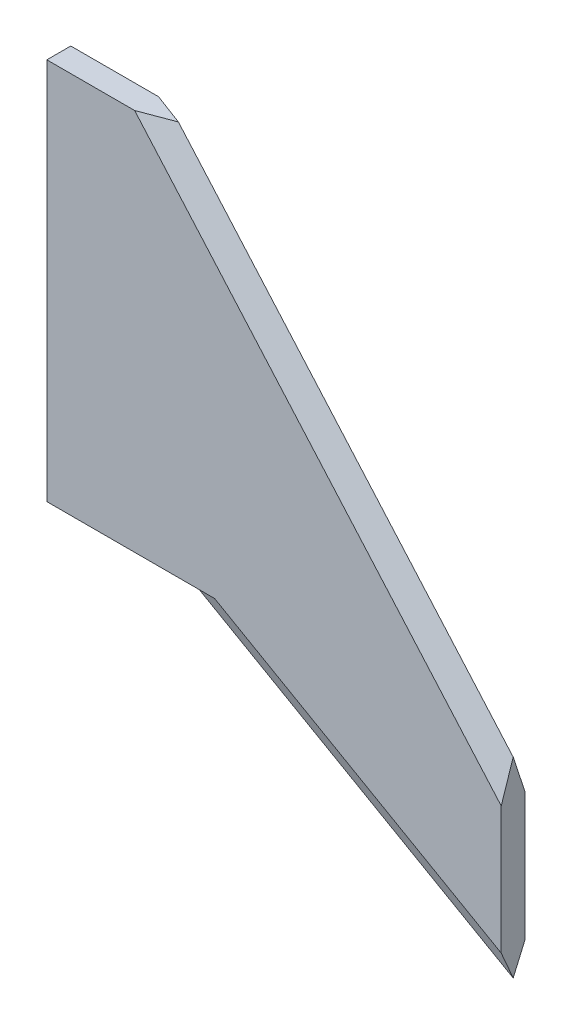
SolidWorks part; units mm, degrees
ref_plane "Front Plane" through (0, 0, 0) normal (0, 0, 1) x (1, 0, 0)
ref_plane "Top Plane" through (0, 0, 0) normal (0, 1, 0) x (1, 0, 0)
ref_plane "Right Plane" through (0, 0, 0) normal (1, 0, 0) x (0, 0, -1)
sketch "Sketch1" plane through (0, 0, 0) normal (0, 0, 1) x (1, 0, 0)
  line L0 (0, 0) -> (0, 80)
  line L1 (0, 80) -> (70, 0)
  line L2 (70, 0) -> (70, -40)
  line L3 (70, -40) -> (0, 0)
  dimension "D1" = 80
  dimension "D2" = 70
  dimension "D3" = 80
  dimension "D4" = 40
extrude "Boss-Extrude1" add sketch "Sketch1" along normal mid plane 5
sketch "Sketch7" plane through (0, 0, 0) normal (-1, 0, 0) x (0, 0, 1)
  line L4 (-2.5, 80) -> (-2.5, 0)
  line L5 (-2.5, 0) -> (2.5, 0)
  line L6 (2.5, 0) -> (2.5, 80)
  line L7 (2.5, 80) -> (-2.5, 80)
  line L8 (-2.5, 80) -> (-2.5, 0)
  line L9 (-2.5, 0) -> (2.5, 0)
  line L10 (2.5, 0) -> (2.5, 80)
  line L11 (2.5, 80) -> (-2.5, 80)
  dimension "D1" = 0
extrude "Boss-Extrude2" add sketch "Sketch7" along normal blind 25
chamfer "Chamfer1" distance 2.5 distance2 5 2 edges at (35, -20, 2.5) (35, 40, 2.5) first distance on face at (35, -20, 0) first distance on face at (35, 40, 0)
chamfer "Chamfer2" distance 5 distance2 2.5 2 edges at (35, -20, -2.5) (35, 40, -2.5) first distance on face at (15, 20, -2.5)
